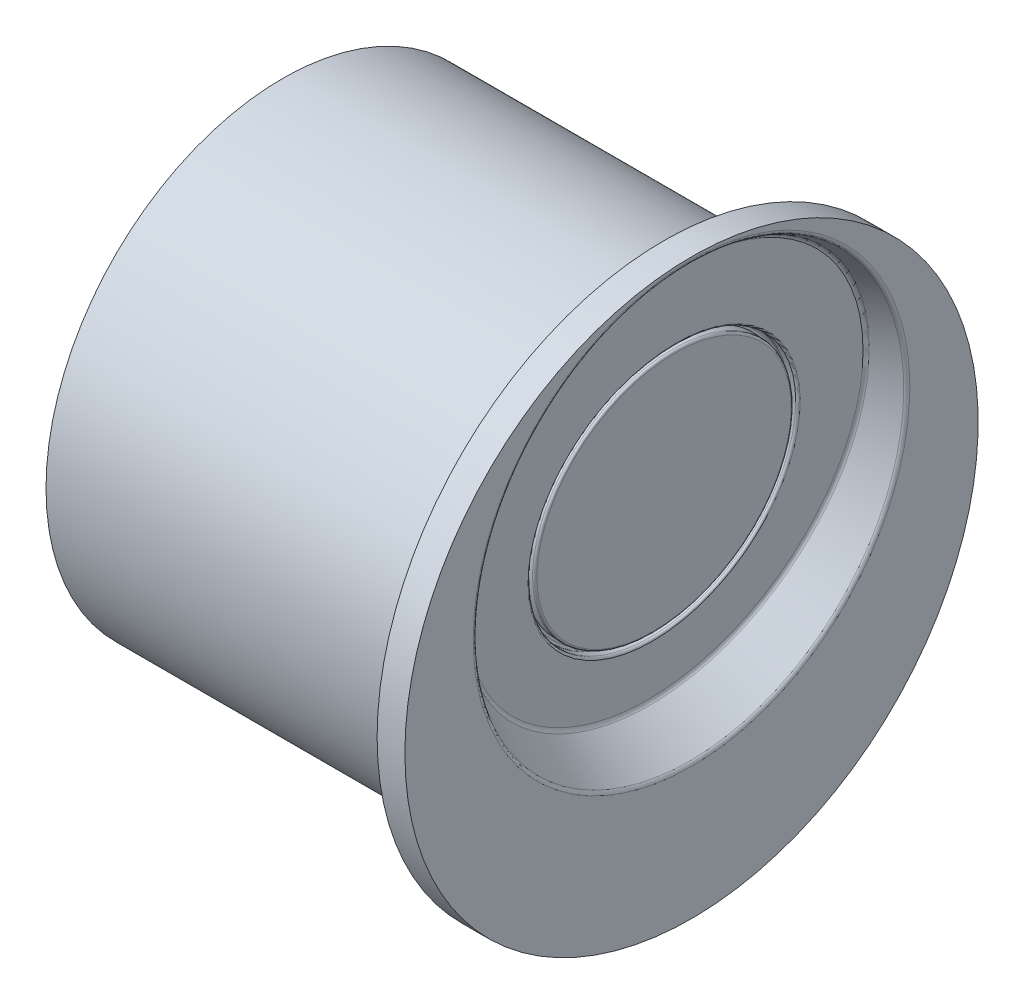
SolidWorks part; units mm, degrees
ref_plane "Спереди" through (0, 0, 0) normal (0, 0, 1) x (1, 0, 0)
ref_plane "Сверху" through (0, 0, 0) normal (0, 1, 0) x (1, 0, 0)
ref_plane "Справа" through (0, 0, 0) normal (1, 0, 0) x (0, 0, -1)
sketch "Эскиз1" plane through (0, 0, 0) normal (0, 0, 1) x (1, 0, 0)
  line L0 (0, 0) -> (49.1875, 0) construction
  line L1 (0, 0) -> (0, 10.65)
  line L2 (0, 10.65) -> (17.15, 10.65)
  line L3 (17.15, 10.65) -> (17.15, 12.9)
  line L4 (17.15, 12.9) -> (18.4, 12.9)
  line L5 (18.4, 12.9) -> (18.4, 0)
  line L6 (18.4, 0) -> (0, 0)
  dimension "D1" = 1.25
  dimension "D2" = 21.3
  dimension "D3" = 18.4
revolve "Повернуть1" add sketch "Эскиз1" angle 360 about L0
ref_plane "Плоскость1" through (9.2, -9.2, 0) normal (0.7071, -0.7071, 0) x (-0.7071, -0.7071, 0)
ref_axis "Ось1" through (18.4, 0, 50) along (0, 0, -1)
ref_plane "Плоскость2" through (18.2602, -1.5976, 0) normal (0.9962, -0.0872, 0) x (0, 0, -1)
sketch "Эскиз2" plane through (18.2602, -1.5976, 0) normal (0.9962, -0.0872, 0) x (0, 0, -1)
  circle A0 centre (0, 4.9824) radius 9
  dimension "D1" = 18
extrude "Вырез-Вытянуть1" cut sketch "Эскиз2" against normal blind 1.5 and the other way through all
draft "Уклон1" type of draft neutral plane draft angle 30 faces to draft 1 face at (17.9846, 12.4624, 0) neutral plane through (17.2002, 3.4966, 0) neutral plane normal (0.9962, -0.0872, 0) parameters "D1"=30
fillet "Скругление1" radius 0.2 2 edges at (17.9846, 12.4624, 0) (18.4, -6.8585, 0)
sketch "Эскиз3" plane through (16.7659, -1.4668, 0) normal (0.9962, -0.0872, 0) x (0, 0, -1)
  circle A0 centre (0, 4.5913) radius 6
  circle A1 centre (0, 4.5913) radius 5.8
  point P0 (0, 4.9824)
  dimension "D1" = 12
  dimension "D2" = 0.2
extrude "Вырез-Вытянуть2" cut sketch "Эскиз3" against normal blind 0.5
fillet "Скругление2" radius 0.1 3 edges at (17.6716, 8.8849, 0) (17.689, 9.0842, 0) (17.1909, 9.1277, 0)
sketch "Эскиз4" plane through (0, 0, 0) normal (-1, 0, 0) x (0, 0, 1)
  circle A0 centre (0, -8.5204) radius 1.5
  dimension "D1" = 3
extrude "Бобышка-Вытянуть1" add sketch "Эскиз4" along normal blind 2
